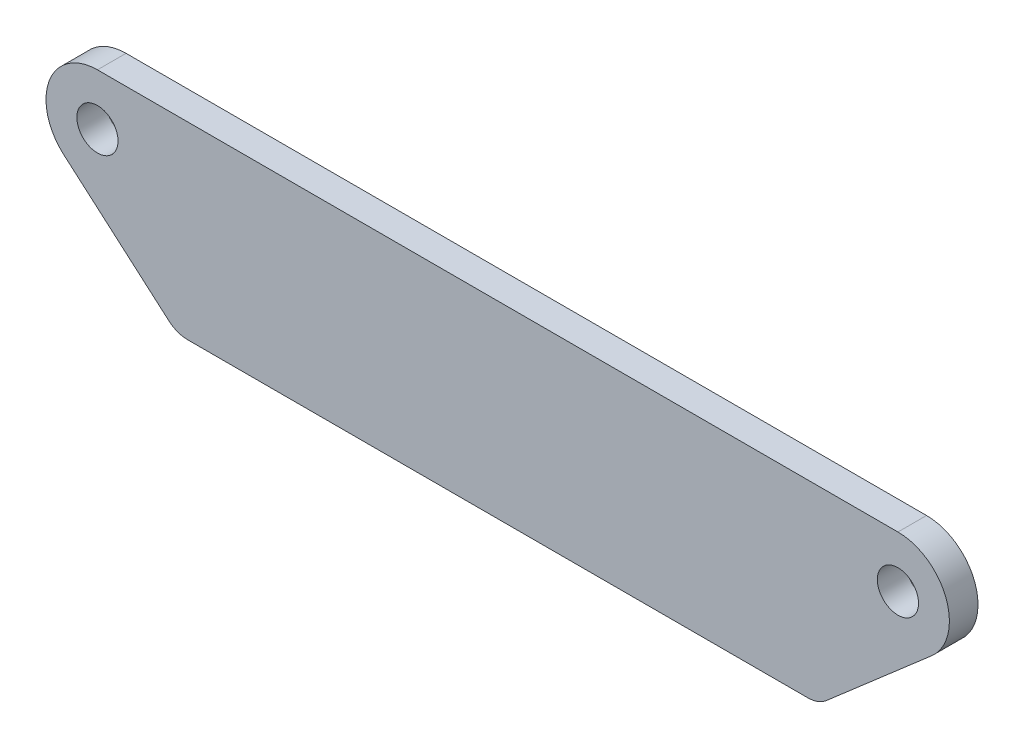
SolidWorks part; units mm, degrees
material "Custom Plastic"
ref_plane "Front Plane" through (0, 0, 0) normal (0, 0, 1) x (1, 0, 0)
ref_plane "Top Plane" through (0, 0, 0) normal (0, 1, 0) x (1, 0, 0)
ref_plane "Right Plane" through (0, 0, 0) normal (1, 0, 0) x (0, 0, -1)
sketch "Sketch1" plane through (0, 0, 0) normal (0, 0, 1) x (1, 0, 0)
  line L0 (0, 6.35) -> (0, -6.35) construction
  line L1 (0, -6.35) -> (88.9, -6.35) construction
  line L2 (88.9, -6.35) -> (0, 6.35) construction
  line L3 (0, 6.35) -> (88.9, 6.35) construction
  line L4 (88.9, 6.35) -> (88.9, -6.35) construction
  line L5 (-3.7475, 2.0352) -> (7.9361, -8.1121)
  line L6 (10.018, -8.89) -> (78.882, -8.89)
  line L8 (92.6475, 2.0352) -> (80.9639, -8.1121)
  line L9 (0, 12.065) -> (88.9, 12.065)
  circle A0 centre (0, 6.35) radius 2.286
  circle A1 centre (0, -6.35) radius 3.8735 construction
  circle A2 centre (88.9, -6.35) radius 3.8735 construction
  circle A3 centre (0, -6.35) radius 5.715 construction
  circle A4 centre (0, 6.35) radius 5.715 construction
  circle A5 centre (88.9, -6.35) radius 5.715 construction
  circle A6 centre (88.9, 6.35) radius 2.286
  circle A7 centre (88.9, 6.35) radius 5.715 construction
  arc A8 (80.9639, -8.1121) -> (78.882, -8.89) centre (78.882, -5.715) cw
  arc A9 (7.9361, -8.1121) -> (10.018, -8.89) centre (10.018, -5.715) ccw
  arc A10 (-3.7475, 2.0352) -> (0, 12.065) centre (0, 6.35) cw
  arc A11 (88.9, 12.065) -> (92.6475, 2.0352) centre (88.9, 6.35) cw
  point P20 (8.8318, -8.89)
  dimension "D1" = 7.747
  dimension "D4" = 11.43
  dimension "D5" = 3.175
  dimension "D6" = 4.572
  dimension "D2" = 12.7
  dimension "D3" = 88.9
  dimension "D7" = 8.89
extrude "Boss-Extrude1" add sketch "Sketch1" along normal blind 3.175
